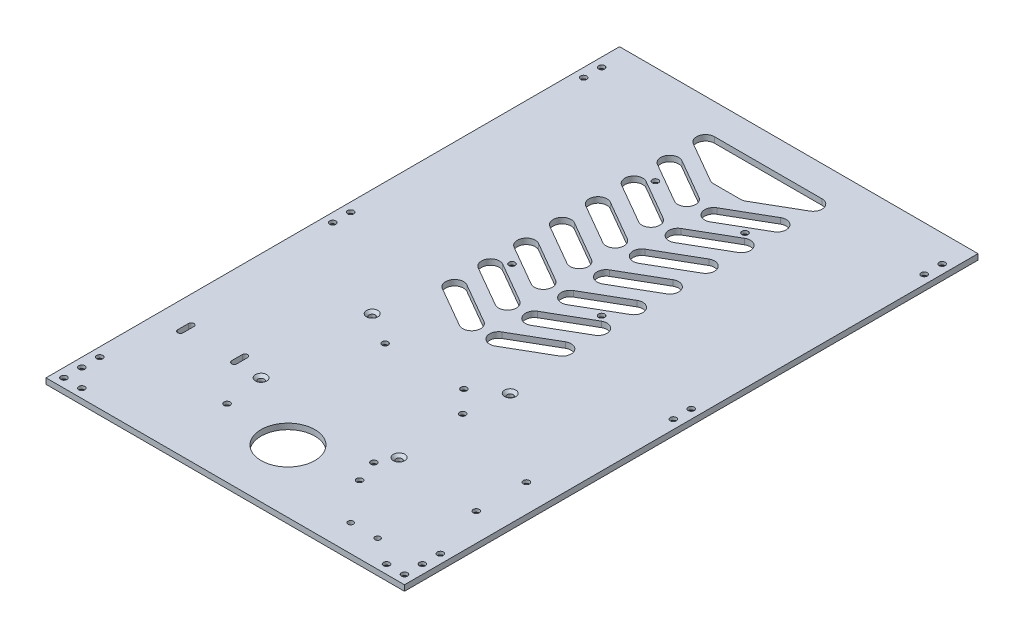
SolidWorks part; units mm, degrees
material "Acrylic (Medium-high impact)"
ref_plane "Front Plane" through (0, 0, 0) normal (0, 0, 1) x (1, 0, 0)
ref_plane "Top Plane" through (0, 0, 0) normal (0, 1, 0) x (1, 0, 0)
ref_plane "Right Plane" through (0, 0, 0) normal (1, 0, 0) x (0, 0, -1)
sketch "Sketch1" plane through (0, 0, 0) normal (0, 1, 0) x (1, 0, 0)
  line L0 (0, -160) -> (0, 160) construction
  line L1 (-100, 160) -> (100, 160)
  line L2 (-100, 160) -> (-100, -160)
  line L3 (-100, -160) -> (100, -160)
  line L4 (100, 160) -> (100, -160)
  line L5 (100, 0) -> (-100, 0) construction
  dimension "D1" = 320
  dimension "D2" = 200
extrude "Boss-Extrude1" add sketch "Sketch1" along normal blind 3.175
hole_wizard "CSK for M3 Flat Head Machine Screw1" positions "Sketch3" profile "Sketch2" countersink size "M3" standard "Ansi Metric" end condition through all
sketch "Sketch3" plane through (0, 0, 0) normal (0, -1, 0) x (1, 0, 0)
  line L0 (-100, 155) -> (-85, 155) construction
  line L1 (-100, -160) -> (-100, 160) construction
  line L3 (-95, 135) -> (-95, 160) construction
  line L4 (-100, 160) -> (100, 160) construction
  line L6 (-100, -160) -> (-100, 160) construction
  line L8 (-95, 135) -> (-95, -160) construction
  line L10 (100, -160) -> (-100, -160) construction
  point P0 (-95, 155)
  point P1 (-85, 155)
  point P3 (-95, 145)
  point P5 (-95, 135)
  point P26 (-95, -145)
  point P28 (-95, -135)
  point P44 (-95, 5)
  point P46 (-95, -5)
  dimension "D1" = 10
  dimension "D2" = 10
  dimension "D3" = 10
  dimension "D4" = 5
  dimension "D5" = 5
  dimension "D6" = 15
  dimension "D7" = 10
  dimension "D8" = 10
  dimension "D9" = 150
sketch "Sketch2" plane through (-95, 0, 155) normal (1, 0, 0) x (0, 0, -1)
  line L0 (0, 0) -> (0, 3.175)
  line L1 (0, 3.175) -> (1.7, 3.175)
  line L2 (1.7, 3.175) -> (1.7, 1.45)
  line L3 (1.7, 1.45) -> (3.15, 0)
  line L5 (3.15, 0) -> (0, 0)
  line L6 (-1.7, 1.45) -> (-3.15, 0) construction
  line L11 (0, -6.35) -> (0, 107.95) construction
  dimension "Thru Hole Dia." = 3.4
  dimension "Thru Hole Depth" = 3.175
  dimension "Near C'Sink Dia." = 6.3
  dimension "Near C'Sink Angle" = 90
mirror "Mirror1" about plane through (0, 0, 0) normal (1, 0, 0) of "CSK for M3 Flat Head Machine Screw1"
hole_wizard "CSK for M3 Flat Head Machine Screw2" positions "Sketch5" profile "Sketch4" countersink size "M3" standard "Ansi Metric" end condition through all
sketch "Sketch5" plane through (0, 0, 0) normal (0, -1, 0) x (1, 0, 0)
  line L9 (-25, -25) -> (25, -25)
  line L10 (-25, -25) -> (-25, -105)
  line L11 (-25, -105) -> (25, -105)
  line L12 (25, -25) -> (25, -105)
  line L13 (100, -160) -> (-100, -160) construction
  line L14 (0, -105) -> (0, -160) construction
  point P160 (-25, -105)
  point P162 (25, -105)
  point P164 (25, -25)
  point P166 (-25, -25)
  dimension "D5" = 50
  dimension "D6" = 80
  dimension "D7" = 55
sketch "Sketch4" plane through (-25, 0, -105) normal (1, 0, 0) x (0, 0, -1)
  line L0 (0, 0) -> (0, 3.175)
  line L1 (0, 3.175) -> (1.7, 3.175)
  line L2 (1.7, 3.175) -> (1.7, 1.45)
  line L3 (1.7, 1.45) -> (3.15, 0)
  line L5 (3.15, 0) -> (0, 0)
  line L6 (-1.7, 1.45) -> (-3.15, 0) construction
  line L11 (0, -6.35) -> (0, 107.95) construction
  dimension "Thru Hole Dia." = 3.4
  dimension "Thru Hole Depth" = 3.175
  dimension "Near C'Sink Dia." = 6.3
  dimension "Near C'Sink Angle" = 90
hole_wizard "CSK for M3 Flat Head Machine Screw3" positions "Sketch7" profile "Sketch6" countersink size "M3" standard "Ansi Metric" end condition through all
sketch "Sketch7" plane through (0, 3.175, 0) normal (0, 1, 0) x (-1, 0, 0)
  line L1 (40, 38) -> (-37, 38) construction
  line L2 (40, 38) -> (40, 100) construction
  line L3 (40, 100) -> (-37, 100) construction
  line L4 (-37, 38) -> (-37, 100) construction
  line L9 (100, -160) -> (100, 160) construction
  line L10 (100, 160) -> (-100, 160) construction
  point P0 (40, 38)
  point P1 (-37, 100)
  point P3 (-37, 38)
  point P5 (40, 100)
  dimension "D1" = 60
  dimension "D2" = 60
  dimension "D3" = 77
  dimension "D4" = 62
sketch "Sketch6" plane through (-40, 3.175, 38) normal (1, 0, 0) x (0, 0, 1)
  line L0 (0, 0) -> (0, 3.175)
  line L1 (0, 3.175) -> (1.7, 3.175)
  line L2 (1.7, 3.175) -> (1.7, 1.45)
  line L3 (1.7, 1.45) -> (3.15, 0)
  line L5 (3.15, 0) -> (0, 0)
  line L6 (-1.7, 1.45) -> (-3.15, 0) construction
  line L11 (0, -6.35) -> (0, 107.95) construction
  dimension "Thru Hole Dia." = 3.4
  dimension "Thru Hole Depth" = 3.175
  dimension "Near C'Sink Dia." = 6.3
  dimension "Near C'Sink Angle" = 90
sketch "Sketch8" plane through (0, 3.175, 0) normal (0, 1, 0) x (1, 0, 0)
  line L2 (0, 160) -> (0, -15) construction
  line L3 (100, 160) -> (-100, 160) construction
  line L4 (0, -15) -> (-7.5, -15) construction
  line L5 (-7.5, -15) -> (-30, -2.0096) construction
  line L6 (-10, -19.3301) -> (-32.5, -6.3397)
  line L7 (-5, -10.6699) -> (-27.5, 2.3205)
  line L8 (7.5, -15) -> (30, -2.0096) construction
  line L9 (10, -19.3301) -> (32.5, -6.3397)
  line L10 (5, -10.6699) -> (27.5, 2.3205)
  arc A0 (10, -19.3301) -> (5, -10.6699) centre (7.5, -15) cw
  arc A1 (-10, -19.3301) -> (-5, -10.6699) centre (-7.5, -15) ccw
  arc A2 (-27.5, 2.3205) -> (-32.5, -6.3397) centre (-30, -2.0096) ccw
  arc A3 (27.5, 2.3205) -> (32.5, -6.3397) centre (30, -2.0096) cw
  point P2 (18.75, -8.5048)
  point P11 (-18.75, -8.5048)
  dimension "D3" = 175
  dimension "D1" = 5
  dimension "D2" = 30
  dimension "D4" = 60
  dimension "D5" = 7.5
extrude "Cut-Extrude1" cut sketch "Sketch8" against normal through all
pattern_linear "LPattern1" count 8 spacing 20 along (0, 0, -1) of "Cut-Extrude1"
sketch "Sketch9" plane through (0, 3.175, 0) normal (0, 1, 0) x (1, 0, 0)
  line L0 (-100, -160) -> (100, -160) construction
  line L2 (-7.5, 120) -> (7.5, 120)
  line L3 (-32.5, 133.6603) -> (-10, 120.6699) construction
  line L6 (10, 120.6699) -> (32.5, 133.6603) construction
  line L7 (-32.5, 133.6603) -> (-10, 120.6699)
  line L8 (0, -160) -> (0, -125) construction
  line L9 (-85, -94) -> (-85, -100) construction
  line L10 (10, 120.6699) -> (32.5, 133.6603)
  line L11 (-30, 142.9904) -> (30, 142.9904)
  line L12 (-83.5, -94) -> (-83.5, -100)
  line L13 (-86.5, -94) -> (-86.5, -100)
  line L14 (-70, -160) -> (-70, -83.9146) construction
  line L15 (-55, -94) -> (-55, -100) construction
  line L16 (-56.5, -94) -> (-56.5, -100)
  line L17 (55, -145) -> (70, -145) construction
  line L18 (100, -160) -> (100, 160) construction
  line L19 (-53.5, -94) -> (-53.5, -100)
  line L20 (-100, 160) -> (-100, -160) construction
  circle A0 centre (0, -125) radius 15
  arc A1 (-10, 120.6699) -> (-5, 129.3301) centre (-7.5, 125) ccw construction
  arc A2 (5, 129.3301) -> (10, 120.6699) centre (7.5, 125) ccw construction
  arc A3 (-27.5, 142.3205) -> (-32.5, 133.6603) centre (-30, 137.9904) ccw construction
  arc A4 (32.5, 133.6603) -> (27.5, 142.3205) centre (30, 137.9904) ccw construction
  arc A5 (-10, 120.6699) -> (-7.5, 120) centre (-7.5, 125) ccw
  arc A6 (-30, 142.9904) -> (-32.5, 133.6603) centre (-30, 137.9904) ccw
  arc A7 (7.5, 120) -> (10, 120.6699) centre (7.5, 125) ccw
  arc A8 (32.5, 133.6603) -> (30, 142.9904) centre (30, 137.9904) ccw
  arc A9 (-83.5, -94) -> (-86.5, -94) centre (-85, -94) ccw
  arc A10 (-86.5, -100) -> (-83.5, -100) centre (-85, -100) ccw
  arc A11 (-56.5, -94) -> (-53.5, -94) centre (-55, -94) cw
  arc A12 (-53.5, -100) -> (-56.5, -100) centre (-55, -100) cw
  circle A13 centre (55, -145) radius 1.5
  circle A14 centre (70, -145) radius 1.5
  point P23 (-85, -97)
  point P32 (-55, -97)
  dimension "D2" = 30
  dimension "D3" = 6
  dimension "D5" = 15
  dimension "D10" = 3
  dimension "D4" = 1.5
  dimension "D6" = 15
  dimension "D7" = 35
  dimension "D8" = 60
  dimension "D9" = 15
  dimension "D11" = 15
  dimension "D12" = 30
extrude "Cut-Extrude2" cut sketch "Sketch9" against normal through all
hole_wizard "CSK for M3 Flat Head Machine Screw4" positions "Sketch12" profile "Sketch11" countersink size "M3" standard "Ansi Metric" end condition through all
sketch "Sketch12" plane through (0, 0, 0) normal (0, -1, 0) x (1, 0, 0)
  line L1 (18.42, 112) -> (87, 112) construction
  line L2 (18.42, 112) -> (18.42, 58.66) construction
  line L3 (18.42, 58.66) -> (87, 58.66) construction
  line L4 (87, 112) -> (87, 58.66) construction
  line L5 (100, 160) -> (100, -160) construction
  line L6 (-100, 160) -> (100, 160) construction
  point P0 (84.46, 104.38)
  point P1 (32.39, 109.46)
  point P3 (33.66, 61.2)
  point P5 (84.46, 76.44)
  dimension "D1" = 13.97
  dimension "D2" = 2.54
  dimension "D3" = 7.62
  dimension "D4" = 66.04
  dimension "D5" = 66.04
  dimension "D6" = 35.56
  dimension "D7" = 15.24
  dimension "D8" = 50.8
  dimension "D9" = 53.34
  dimension "D10" = 68.58
  dimension "D11" = 13
  dimension "D12" = 48
sketch "Sketch11" plane through (84.46, 0, 104.38) normal (1, 0, 0) x (0, 0, -1)
  line L0 (0, 0) -> (0, 3.175)
  line L1 (0, 3.175) -> (1.7, 3.175)
  line L2 (1.7, 3.175) -> (1.7, 1.45)
  line L3 (1.7, 1.45) -> (3.15, 0)
  line L5 (3.15, 0) -> (0, 0)
  line L6 (-1.7, 1.45) -> (-3.15, 0) construction
  line L11 (0, -6.35) -> (0, 107.95) construction
  dimension "Thru Hole Dia." = 3.4
  dimension "Thru Hole Depth" = 3.175
  dimension "Near C'Sink Dia." = 6.3
  dimension "Near C'Sink Angle" = 90
hole_wizard "CSK for M3 Flat Head Machine Screw5" positions "Sketch14" profile "Sketch13" countersink size "M3" standard "Ansi Metric" end condition through all
sketch "Sketch14" plane through (0, 0, 0) normal (0, -1, 0) x (1, 0, 0)
  line L0 (37, 122) -> (-37, 122) construction
  line L1 (-37, 122) -> (0, 122) construction
  line L3 (-22, 48.8221) -> (22, 48.8221) construction
  line L5 (0, 48.8221) -> (0, 122) construction
  line L7 (0, 122) -> (0, 160) construction
  line L8 (-100, 160) -> (100, 160) construction
  point P0 (-37, 122)
  point P1 (37, 122)
  point P3 (22, 48.8221)
  point P5 (-22, 48.8221)
  dimension "D1" = 37
  dimension "D2" = 22
  dimension "D3" = 94
  dimension "D4" = 38
sketch "Sketch13" plane through (-37, 0, 122) normal (1, 0, 0) x (0, 0, -1)
  line L0 (0, 0) -> (0, 3.175)
  line L1 (0, 3.175) -> (1.7, 3.175)
  line L2 (1.7, 3.175) -> (1.7, 1.45)
  line L3 (1.7, 1.45) -> (3.15, 0)
  line L5 (3.15, 0) -> (0, 0)
  line L6 (-1.7, 1.45) -> (-3.15, 0) construction
  line L11 (0, -6.35) -> (0, 107.95) construction
  dimension "Thru Hole Dia." = 3.4
  dimension "Thru Hole Depth" = 3.175
  dimension "Near C'Sink Dia." = 6.3
  dimension "Near C'Sink Angle" = 90
